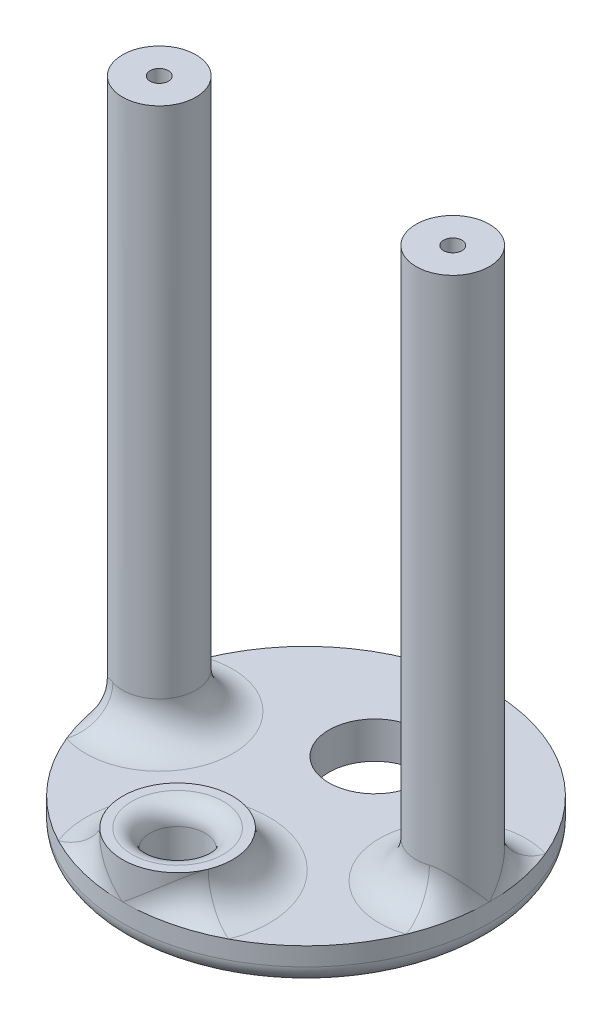
SolidWorks part; units mm, degrees
ref_plane "Front Plane" through (0, 0, 0) normal (0, 0, 1) x (1, 0, 0)
ref_plane "Top Plane" through (0, 0, 0) normal (0, 1, 0) x (1, 0, 0)
ref_plane "Right Plane" through (0, 0, 0) normal (1, 0, 0) x (0, 0, -1)
sketch "Sketch1" plane through (0, 0, 0) normal (0, 1, 0) x (1, 0, 0)
  circle A0 centre (0, 0) radius 20
  circle A1 centre (0, 7.5) radius 10.5 construction
  circle A2 centre (0, 7.5) radius 5
  circle A3 centre (0, 7.5) radius 12.5 construction
  circle A4 centre (0, -14) radius 3
  circle A5 centre (0, -14) radius 6
  circle A6 centre (16, 0) radius 4
  circle A7 centre (-16, 0) radius 4
  circle A8 centre (-16, 0) radius 1
  circle A9 centre (16, 0) radius 1
  point P15 (0, 0)
  point P16 (0, 0)
  point P17 (14.7009, 0)
  point P18 (0, 0)
  dimension "D1" = 40
  dimension "D3" = 10
  dimension "D4" = 25
  dimension "D5" = 6
  dimension "D7" = 8
  dimension "D8" = 8
  dimension "D2" = 21
  dimension "D6" = 3
  dimension "D9" = 3
  dimension "D10" = 3
extrude "Boss-Extrude6" add sketch "Sketch1" against normal blind 4 contours A0 A7 A5 A6 A2 | A7 A8 | A5 A4 | A6 A9 | A8 | A9 region at (-16, 0, -3.8869) region at (-4.1226, 0, 9.8774) region at (0, 0, -1.0309) region at (12.1131, 0, 0) region at (-16, 0, 0) region at (16, 0, 0)
extrude "Boss-Extrude7" add sketch "Sketch1<6>" along normal blind 4 contours A5 A4 region at (-4.1226, 0, 9.8774)
sketch "Sketch1<6>" plane through (0, 0, 0) normal (0, 1, 0) x (1, 0, 0) same geometry as "Sketch1"
extrude "Boss-Extrude8" add sketch "Sketch1<7>" along normal blind 60 contours A7 A8 | A6 A9 region at (-16, 0, -3.8869) region at (12.1131, 0, 0)
sketch "Sketch1<7>" plane through (0, 0, 0) normal (0, 1, 0) x (1, 0, 0) same geometry as "Sketch1"
fillet "Fillet2" radius 4 3 edges at (0, 0, 20) (16, 0, 4) (-16, 0, 4)
fillet "Fillet3" radius 2 2 edges at (0, -4, 20) (0, 4, 17)
